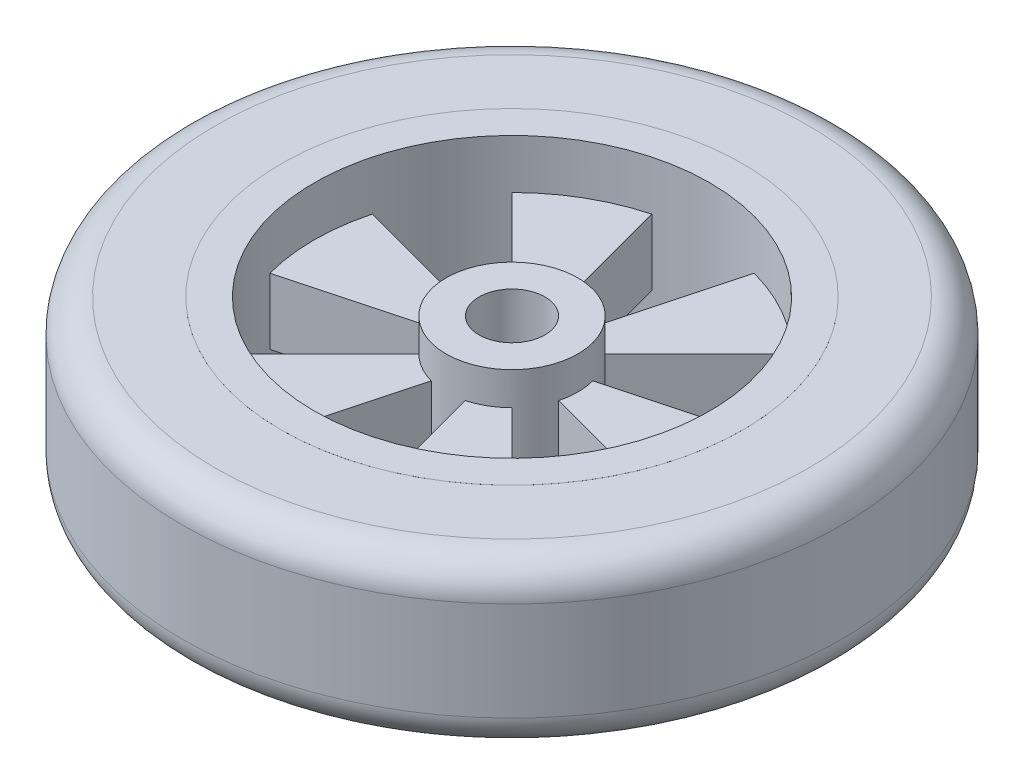
SolidWorks part; units mm, degrees
ref_plane "前视基准面" through (0, 0, 0) normal (0, 0, 1) x (1, 0, 0)
ref_plane "上视基准面" through (0, 0, 0) normal (0, 1, 0) x (1, 0, 0)
ref_plane "右视基准面" through (0, 0, 0) normal (1, 0, 0) x (0, 0, -1)
sketch "草图1" plane through (0, 0, 0) normal (0, 1, 0) x (1, 0, 0)
  circle A0 centre (0, 0) radius 70
  dimension "D1" = 140
extrude "凸台-拉伸1" add sketch "草图1" along normal blind 10 and the other way blind 10
sketch "草图2" plane through (0, 0, 0) normal (0, 1, 0) x (1, 0, 0)
  circle A0 centre (0, 0) radius 20
  dimension "D1" = 40
extrude "凸台-拉伸2" add sketch "草图2" along normal blind 20 and the other way blind 20 separate body
sketch "草图3" plane through (0, 0, 0) normal (0, 1, 0) x (1, 0, 0)
  circle A0 centre (0, 0) radius 70 construction
  circle A1 centre (0, 0) radius 70
  circle A2 centre (0, 0) radius 60
  dimension "D1" = 10
extrude "凸台-拉伸3" add sketch "草图3" along normal blind 25 and the other way blind 25
sketch "草图4" plane through (0, 0, 0) normal (0, 1, 0) x (1, 0, 0)
  circle A0 centre (0, 0) radius 10
  dimension "D1" = 20
extrude "切除-拉伸1" cut sketch "草图4" against normal blind 25 and the other way blind 25
sketch "草图5" plane through (0, 0, 0) normal (0, 1, 0) x (1, 0, 0)
  line L0 (0, 20) -> (0, 60) construction
  line L1 (5.1764, 19.3185) -> (15.5291, 57.9555)
  line L2 (-15.5291, 57.9555) -> (-5.1764, 19.3185)
  line L3 (-5.1764, 19.3185) -> (0, 0) construction
  line L4 (5.1764, 19.3185) -> (0, 0) construction
  circle A0 centre (0, 0) radius 60 construction
  circle A1 centre (0, 0) radius 20 construction
  circle A3 centre (0, 0) radius 20 construction
  arc A4 (5.1764, 19.3185) -> (-5.1764, 19.3185) centre (0, 0) ccw
  arc A5 (15.5291, 57.9555) -> (-15.5291, 57.9555) centre (0, 0) ccw
  dimension "D1" = 15
  dimension "D2" = 15
extrude "切除-拉伸2" cut sketch "草图5" against normal blind 25 and the other way blind 25
ref_axis "基准轴1" through (0, 20, 0) along (0, -1, 0)
pattern_circular "阵列(圆周)1" count 6 over 360 about axis through (0, 20, 0) along (0, -1, 0) of "切除-拉伸2"
sketch "草图6" plane through (0, 0, 0) normal (0, 1, 0) x (1, 0, 0)
  circle A0 centre (0, 0) radius 70 construction
  circle A1 centre (0, 0) radius 70
  circle A2 centre (0, 0) radius 100
  dimension "D1" = 30
extrude "凸台-拉伸4" add sketch "草图6" along normal blind 24.99 and the other way blind 24.99
fillet "圆角1" radius 10 2 edges at (0, -24.99, 100) (0, 24.99, 100)
